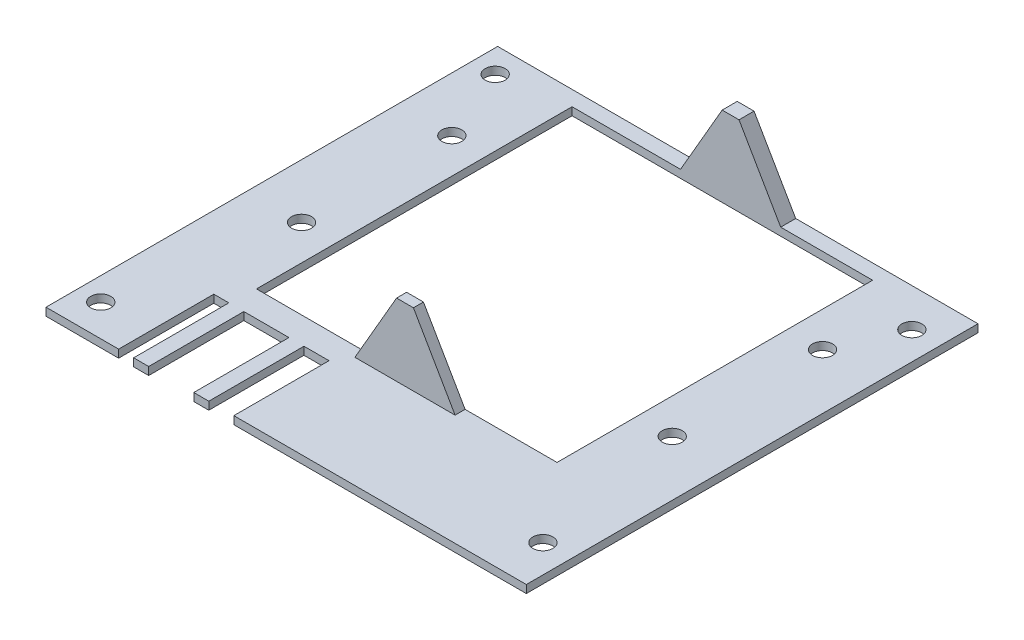
SolidWorks part; units mm, degrees
material "ABS"
ref_plane "Front Plane" through (0, 0, 0) normal (0, 0, 1) x (1, 0, 0)
ref_plane "Top Plane" through (0, 0, 0) normal (0, 1, 0) x (1, 0, 0)
ref_plane "Right Plane" through (0, 0, 0) normal (1, 0, 0) x (0, 0, -1)
sketch "Sketch1" plane through (0, 0, 0) normal (0, 1, 0) x (1, 0, 0)
  line L1 (-32.2441, 108.719) -> (64.6459, 108.719)
  line L2 (-32.2441, 108.719) -> (-32.2441, 18.549)
  line L3 (-32.2441, 18.549) -> (64.6459, 18.549)
  line L4 (64.6459, 108.719) -> (64.6459, 18.549)
  dimension "D1" = 96.89
  dimension "D2" = 90.17
extrude "PCB" add sketch "Sketch1" along normal blind 1.57
sketch "Sketch2" plane through (0, 1.57, 0) normal (0, 1, 0) x (1, 0, 0)
  line L1 (-32.2441, 18.549) -> (64.6459, 18.549) construction
  line L2 (-32.2441, 108.719) -> (-32.2441, 18.549) construction
  line L3 (-32.2441, 18.549) -> (64.6459, 18.549) construction
  circle A0 centre (58.5659, 27.439) radius 2
  circle A1 centre (-27.1641, 24.899) radius 2
  circle A2 centre (-27.1641, 103.639) radius 2
  circle A3 centre (58.5659, 101.099) radius 2
  dimension "D3" = 4
  dimension "D6" = 4
  dimension "D11" = 4
  dimension "D12" = 4
  dimension "D2" = 90.81
  dimension "D4" = 90.81
  dimension "D5" = 6.35
  dimension "D7" = 5.08
  dimension "D8" = 5.08
  dimension "D9" = 82.55
  dimension "D10" = 85.09
  dimension "D13" = 8.89
extrude "M3 Mounting Holes" cut sketch "Sketch2" against normal blind 1.57
sketch "Sketch3" plane through (0, 1.57, 0) normal (0, 1, 0) x (1, 0, 0)
  line L0 (64.6459, 108.719) -> (-32.2441, 108.719) construction
  line L1 (12.7559, 108.719) -> (22.7559, 108.719)
  line L2 (12.7559, 108.719) -> (12.7559, 105.719)
  line L3 (12.7559, 105.719) -> (22.7559, 105.719)
  line L4 (22.7559, 108.719) -> (22.7559, 105.719)
  line L5 (-32.2441, 108.719) -> (-32.2441, 18.549) construction
  line L7 (12.7559, 42.719) -> (22.7559, 42.719)
  line L8 (12.7559, 42.719) -> (12.7559, 40.719)
  line L9 (12.7559, 40.719) -> (22.7559, 40.719)
  line L10 (22.7559, 42.719) -> (22.7559, 40.719)
  dimension "D1" = 3
  dimension "D2" = 10
  dimension "D3" = 0
  dimension "D4" = 45
  dimension "D5" = 63
  dimension "D6" = 2
  dimension "D7" = 45
extrude "Boss-Extrude1" [suppressed] add sketch "Sketch3" along normal blind 10
sketch "Sketch4" plane through (0, 1.57, 0) normal (0, 1, 0) x (1, 0, 0)
  line L0 (64.6459, 108.719) -> (-32.2441, 108.719) construction
  line L1 (64.6459, 108.719) -> (-32.2441, 108.719) construction
  line L2 (-32.2441, 108.719) -> (-32.2441, 18.549) construction
  line L3 (64.6459, 108.719) -> (-32.2441, 108.719) construction
  circle A0 centre (-20.8941, 88.719) radius 2
  circle A1 centre (53.1059, 88.719) radius 2
  circle A2 centre (-20.8941, 58.719) radius 2
  circle A3 centre (53.1059, 58.719) radius 2
  dimension "D1" = 4
  dimension "D2" = 4
  dimension "D7" = 4
  dimension "D8" = 4
  dimension "D12" = 74
  dimension "D3" = 20
  dimension "D4" = 20
  dimension "D5" = 74
  dimension "D6" = 11.35
  dimension "D9" = 50
  dimension "D10" = 50
  dimension "D11" = 11.35
extrude "Cut-Extrude1" cut sketch "Sketch4" against normal blind 23
ref_plane "Plane1" through (0, 0, -42.719) normal (0, 0, 1) x (1, 0, 0)
sketch "Sketch7" plane through (0, 0, -42.719) normal (0, 0, 1) x (1, 0, 0)
  line L0 (27.7559, 1.57) -> (19.4384, 15.9764)
  line L1 (19.4384, 15.9764) -> (16.0735, 15.9764)
  line L2 (16.0735, 15.9764) -> (7.7559, 1.57)
  line L3 (7.7559, 1.57) -> (27.7559, 1.57)
  line L4 (-32.2441, 1.57) -> (64.6459, 1.57) construction
  dimension "D1" = 60
  dimension "D2" = 60
  dimension "D3" = 0
  dimension "D4" = 3.3649
  dimension "D5" = 20
  dimension "D6" = 5
ref_plane "Plane2" through (0, 0, -108.719) normal (0, 0, 1) x (1, 0, 0)
sketch "Sketch8" plane through (0, 0, -108.719) normal (0, 0, 1) x (1, 0, 0)
  line L0 (27.7559, 1.57) -> (19.4384, 15.9764) construction
  line L1 (19.4384, 15.9764) -> (16.0735, 15.9764) construction
  line L2 (16.0735, 15.9764) -> (7.7559, 1.57) construction
  line L3 (7.7559, 1.57) -> (27.7559, 1.57) construction
  line L4 (27.7559, 1.57) -> (19.4384, 15.9764)
  line L5 (19.4384, 15.9764) -> (16.0735, 15.9764)
  line L6 (16.0735, 15.9764) -> (7.7559, 1.57)
  line L7 (7.7559, 1.57) -> (27.7559, 1.57)
extrude "Boss-Extrude2" add sketch "Sketch7" along normal blind 2
extrude "Boss-Extrude3" add sketch "Sketch8" along normal blind 3
sketch "Sketch9" plane through (0, 1.57, 0) normal (0, 1, 0) x (1, 0, 0)
  line L0 (-32.2441, 18.549) -> (64.6459, 18.549) construction
  line L1 (-14.2441, 18.549) -> (-17.2441, 18.549)
  line L2 (-14.2441, 18.549) -> (-14.2441, 37.549)
  line L3 (-14.2441, 37.549) -> (-17.2441, 37.549)
  line L4 (-17.2441, 18.549) -> (-17.2441, 37.549)
  line L5 (-32.2441, 108.719) -> (-32.2441, 18.549) construction
  line L6 (-11.2441, 18.549) -> (-2.2441, 18.549)
  line L7 (-11.2441, 18.549) -> (-11.2441, 37.549)
  line L8 (-11.2441, 37.549) -> (-2.2441, 37.549)
  line L9 (-2.2441, 18.549) -> (-2.2441, 37.549)
  line L11 (0.7559, 18.549) -> (5.7559, 18.549)
  line L12 (0.7559, 18.549) -> (0.7559, 37.549)
  line L13 (0.7559, 37.549) -> (5.7559, 37.549)
  line L14 (5.7559, 18.549) -> (5.7559, 37.549)
  dimension "D1" = 19
  dimension "D2" = 19
  dimension "D3" = 3
  dimension "D4" = 3
  dimension "D5" = 9
  dimension "D6" = 15
  dimension "D7" = 5
  dimension "D8" = 19
  dimension "D9" = 3
extrude "Cut-Extrude2" cut sketch "Sketch9" against normal through all
sketch "Sketch10" plane through (0, 1.57, 0) normal (0, 1, 0) x (1, 0, 0)
  line L0 (7.7559, 108.719) -> (-32.2441, 108.719) construction
  line L1 (-32.2441, 18.549) -> (-31.7441, 18.549)
  line L2 (-32.2441, 18.549) -> (-32.2441, 108.719)
  line L3 (-32.2441, 108.719) -> (-31.7441, 108.719)
  line L4 (-31.7441, 18.549) -> (-31.7441, 108.719)
  line L5 (64.6459, 108.719) -> (27.7559, 108.719) construction
  line L6 (64.6459, 18.549) -> (64.1459, 18.549)
  line L7 (64.6459, 18.549) -> (64.6459, 108.719)
  line L8 (64.6459, 108.719) -> (64.1459, 108.719)
  line L9 (64.1459, 18.549) -> (64.1459, 108.719)
  dimension "D1" = 0.5
  dimension "D2" = 0.5
extrude "Cut-Extrude3" cut sketch "Sketch10" against normal blind 10
sketch "Sketch11" plane through (0, 1.57, 0) normal (0, 1, 0) x (1, 0, 0)
  line L0 (7.7559, 105.719) -> (27.7559, 105.719) construction
  line L1 (-13.8941, 105.719) -> (46.1059, 105.719)
  line L2 (-13.8941, 105.719) -> (-13.8941, 42.719)
  line L3 (-13.8941, 42.719) -> (46.1059, 42.719)
  line L4 (46.1059, 105.719) -> (46.1059, 42.719)
  dimension "D1" = 60
  dimension "D2" = 63
  dimension "D3" = 0
  dimension "D4" = 7
extrude "Cut-Extrude4" cut sketch "Sketch11" against normal blind 10
